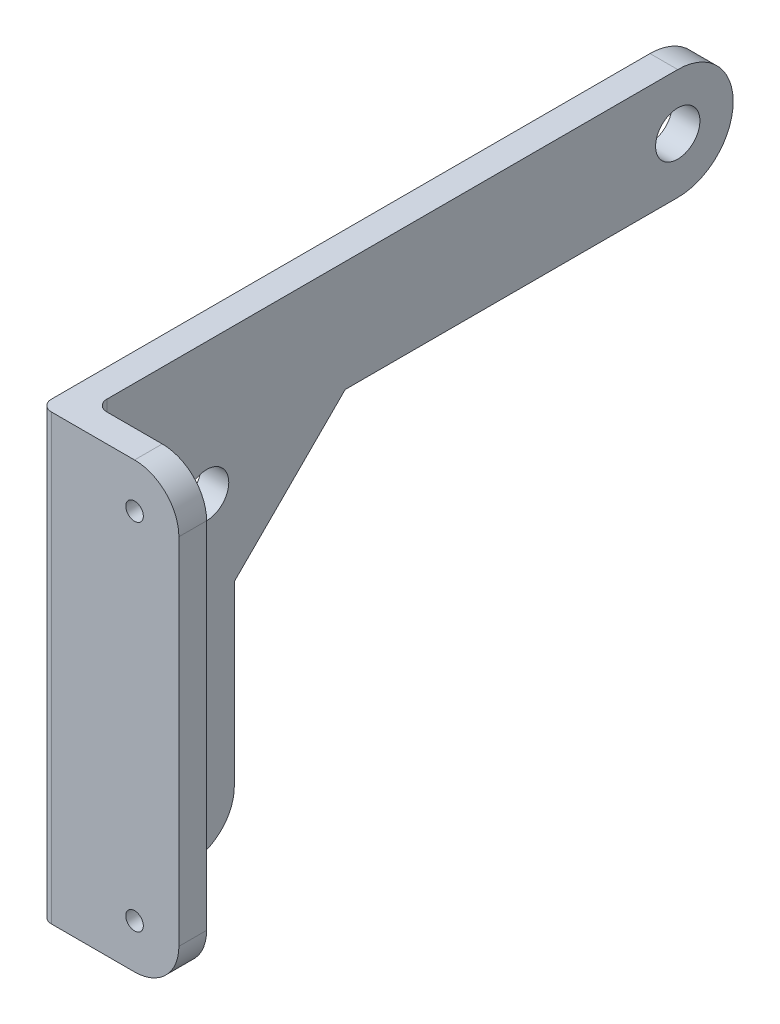
SolidWorks part; units mm, degrees
ref_plane "Front Plane" through (0, 0, 0) normal (0, 0, 1) x (1, 0, 0)
ref_plane "Top Plane" through (0, 0, 0) normal (0, 1, 0) x (1, 0, 0)
ref_plane "Right Plane" through (0, 0, 0) normal (1, 0, 0) x (0, 0, -1)
sketch "Sketch1" plane through (0, 0, 0) normal (1, 0, 0) x (0, 0, -1)
  line L0 (0, 0) -> (-400, 0) construction
  line L1 (0, 50) -> (-550, 50)
  line L2 (0, -50) -> (-400, -50)
  line L3 (-550, -350) -> (-550, 50)
  line L4 (0, 50) -> (-400, 50) construction
  line L5 (-400, -50) -> (-400, -350)
  line L6 (-400, -350) -> (-550, -350)
  circle A0 centre (0, 0) radius 20
  arc A1 (0, 50) -> (0, -50) centre (0, 0) cw
  circle A2 centre (-425, -70) radius 20
  dimension "D4" = 40
  dimension "D3" = 400
  dimension "D5" = 400
  dimension "D6" = 150
  dimension "D7" = 25
  dimension "D8" = 120
  dimension "D1" = 50
  dimension "D2" = 50
extrude "Extrude1" add sketch "Sketch1" along normal mid plane 25
sketch "Sketch2" plane through (12.5, 0, 0) normal (1, 0, 0) x (0, 0, -1)
  line L0 (-550, -350) -> (-400, -350) construction
  line L1 (-550, 50) -> (-525, 50)
  line L2 (-550, 50) -> (-550, -350)
  line L3 (-550, -350) -> (-525, -350)
  line L4 (-525, 50) -> (-525, -350)
  dimension "D1" = 25
extrude "Extrude2" add sketch "Sketch2" along normal blind 100
fillet "Fillet1" radius 40 3 edges at (112.5, -350, 537.5) (112.5, 50, 537.5) (0, -350, 400)
hole_wizard "5/8 (0.625) Diameter Hole1" positions "Sketch5" profile "Sketch4" hole size "5/8" standard "Ansi Inch" end condition through all
sketch "Sketch5" plane through (0, 0, 550) normal (0, 0, 1) x (1, 0, 0)
  point P0 (72.5, 10)
  point P8 (72.5, -310)
sketch "Sketch4" plane through (72.5, 10, 550) normal (1, 0, 0) x (0, -1, 0)
  line L0 (0, 0) -> (0, 600)
  line L1 (0, 600) -> (7.9375, 600)
  line L2 (7.9375, 600) -> (7.9375, 0)
  line L5 (7.9375, 0) -> (0, 0)
  line L11 (0, -6.35) -> (0, 107.95) construction
  dimension "Thru Hole Dia." = 15.875
  dimension "Thru Hole Depth" = 600
ref_axis "Axis1" through (0, 0, 400) along (0, 0, -1)
chamfer "Chamfer1" distance 100 angle 45 1 edges at (0, -50, 400)
fillet "Fillet2" radius 10 2 edges at (-12.5, -150, 550)
